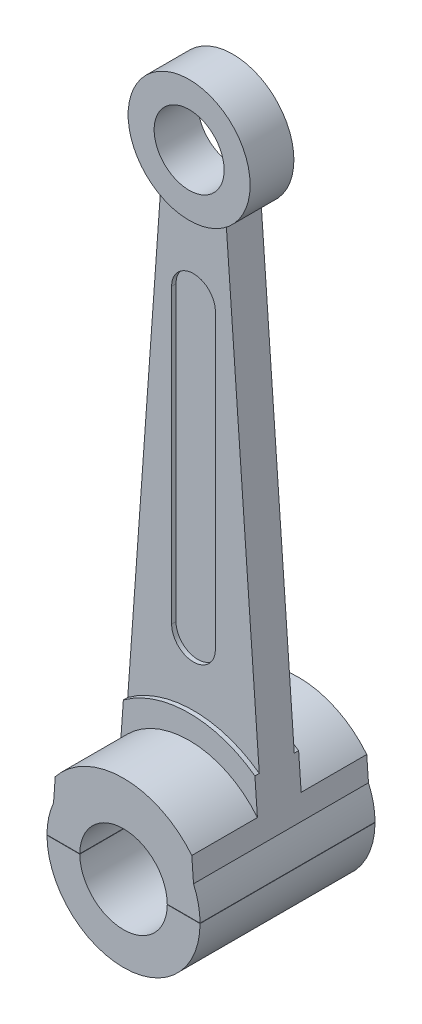
SolidWorks part; units mm, degrees
ref_plane "Front Plane" through (0, 0, 0) normal (0, 0, 1) x (1, 0, 0)
ref_plane "Top Plane" through (0, 0, 0) normal (0, 1, 0) x (1, 0, 0)
ref_plane "Right Plane" through (0, 0, 0) normal (1, 0, 0) x (0, 0, -1)
sketch "Sketch1" plane through (0, 0, 0) normal (0, 0, 1) x (1, 0, 0)
  line L0 (0, 347.726) -> (0, 0) construction
  line L1 (-19.05, 317.8497) -> (-41.91, 49.0496)
  line L2 (19.05, 317.8497) -> (41.91, 49.0496)
  line L3 (0, 271.526) -> (0, 101.6) construction
  line L4 (12.7, 271.526) -> (12.7, 101.6)
  line L5 (-12.7, 271.526) -> (-12.7, 101.6)
  circle A0 centre (0, 0) radius 64.516
  circle A1 centre (0, 0) radius 25.4
  circle A2 centre (0, 347.726) radius 35.433
  circle A3 centre (0, 347.726) radius 20.32
  arc A4 (12.7, 271.526) -> (-12.7, 271.526) centre (0, 271.526) ccw
  arc A5 (-12.7, 101.6) -> (12.7, 101.6) centre (0, 101.6) ccw
  point P13 (0, 186.563)
  dimension "D1" = 129.032
  dimension "D2" = 50.8
  dimension "D3" = 40.64
  dimension "D4" = 70.866
  dimension "D7" = 12.7
  dimension "D5" = 347.726
  dimension "D6" = 38.1
  dimension "D8" = 76.2
  dimension "D9" = 101.6
  dimension "D10" = 83.82
extrude "Boss-Extrude1" add sketch "Sketch1" along normal mid plane 25.4 contours A2 A3 | A0 A1 region at (-16.5548, 377.9157, 0) region at (0, 62.6912, 0)
extrude "Boss-Extrude2" add sketch "Sketch1<3>" along normal mid plane 20.32 contours A2 L1 A0 L2 A5 L5 A4 L4 region at (0, 309.4773, 0)
sketch "Sketch1<3>" plane through (0, 0, 0) normal (0, 0, 1) x (1, 0, 0) same geometry as "Sketch1"
extrude "Boss-Extrude3" add sketch "Sketch1<4>" along normal mid plane 15.24 contours L5 A5 L4 A4 region at (0, 186.563, 0)
sketch "Sketch1<4>" plane through (0, 0, 0) normal (0, 0, 1) x (1, 0, 0) same geometry as "Sketch1"
sketch "Sketch2" plane through (0, 0, 12.7) normal (0, 0, 1) x (1, 0, 0)
  circle A0 centre (0, 0) radius 25.4
  circle A1 centre (0, 0) radius 50.8
  dimension "D1" = 101.6
  dimension "D2" = 50.8
extrude "Boss-Extrude4" add sketch "Sketch2" along normal blind 38.1 and the other way blind 63.5
sketch "Sketch3" plane through (0, 0, 0) normal (0, 0, 1) x (1, 0, 0)
  line L0 (-19.05, 317.8497) -> (-70.877, 53.6625)
  line L1 (19.05, 317.8497) -> (70.877, 53.6625)
  line L2 (-40.64, 18.0054) -> (-19.05, 317.8497)
  line L3 (40.64, 18.0054) -> (19.05, 317.8497)
  arc A0 (-40.64, 18.0054) -> (40.64, 18.0054) centre (0, 0) ccw
  arc A1 (-70.877, 53.6625) -> (70.877, 53.6625) centre (0, 0) ccw
  dimension "D2" = 44.45
  dimension "D3" = 88.9
  dimension "D1" = 81.28
extrude "Cut-Extrude1" cut sketch "Sketch3" against normal mid plane 162.56
sketch "Sketch4" plane through (0, 0, 0) normal (0, 0, 1) x (1, 0, 0)
  line L0 (0, 0) -> (139.6062, 0) construction
  line L2 (357.871, 0.1016) -> (-78.6587, 0.1016)
  line L3 (357.871, 0.1016) -> (357.871, -0.1016)
  line L4 (357.871, -0.1016) -> (-78.6587, -0.1016)
  line L5 (-78.6587, 0.1016) -> (-78.6587, -0.1016)
  line L6 (357.871, 0.1016) -> (-78.6587, -0.1016) construction
  line L7 (357.871, -0.1016) -> (-78.6587, 0.1016) construction
  dimension "D1" = 0.2032
extrude "Cut-Extrude2" cut sketch "Sketch4" against normal mid plane 162.56
